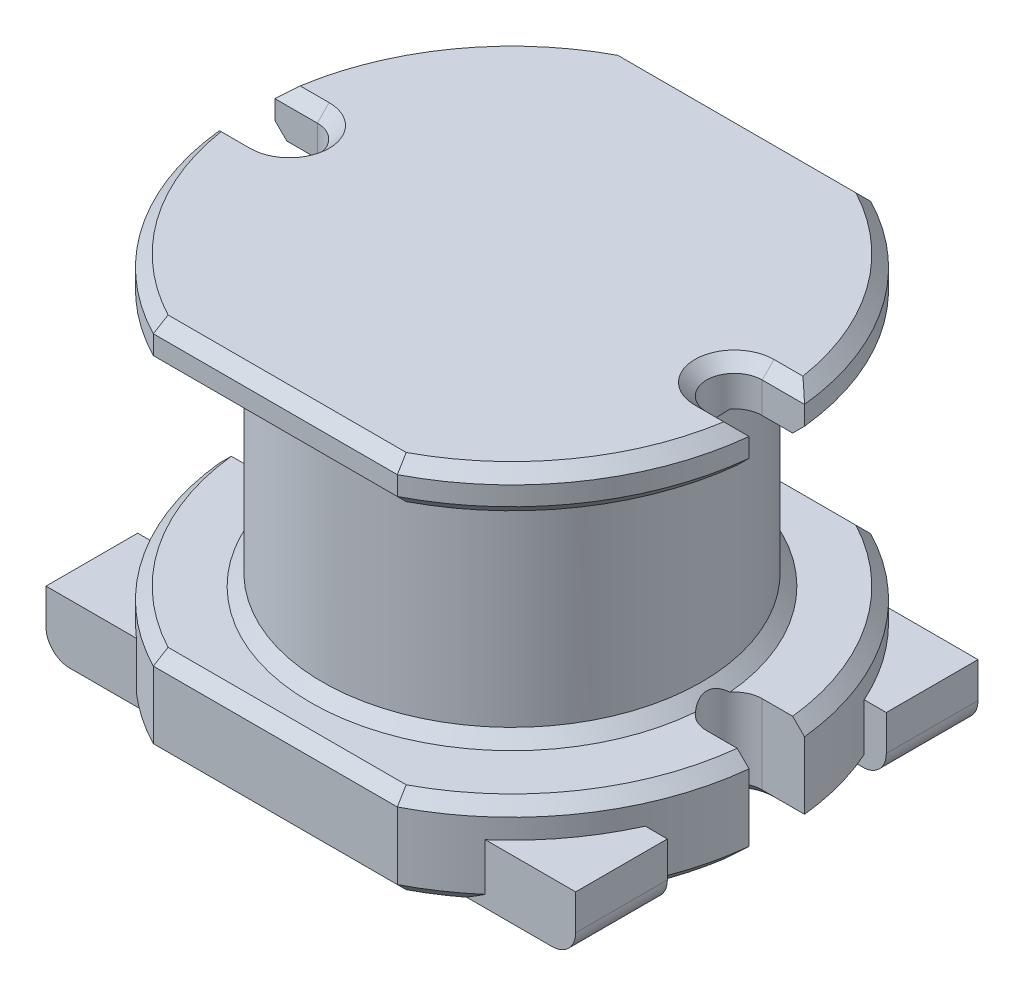
SolidWorks part; units mm, degrees
ref_plane "Спереди" through (0, 0, 0) normal (0, 0, 1) x (1, 0, 0)
ref_plane "Сверху" through (0, 0, 0) normal (0, 1, 0) x (1, 0, 0)
ref_plane "Справа" through (0, 0, 0) normal (1, 0, 0) x (0, 0, -1)
sketch "Эскиз1" plane through (0, 0, 0) normal (0, 0, 1) x (1, 0, 0)
  line L0 (0, 0) -> (2.25, 0)
  line L1 (2.25, 0) -> (2.25, 0.7678)
  line L2 (2.25, 0.7678) -> (1.6023, 0.7678)
  line L3 (1.6023, 0.7678) -> (1.6023, 2.84)
  line L4 (1.6023, 2.84) -> (2.25, 2.84)
  line L5 (2.25, 2.84) -> (2.25, 3.2)
  line L6 (2.25, 3.2) -> (0, 3.2)
  line L7 (0, 3.2) -> (0, 0)
  dimension "D1" = 2.25
  dimension "D2" = 3.2
revolve "Повернуть1" add sketch "Эскиз1" angle 360 about L7
sketch "Эскиз2" plane through (0, 3.2, 0) normal (0, 1, 0) x (1, 0, 0)
  line L1 (-2.25, -2) -> (2.25, -2)
  line L2 (-2.25, -2) -> (-2.25, 2)
  line L3 (-2.25, 2) -> (2.25, 2)
  line L4 (2.25, -2) -> (2.25, 2)
  line L5 (-2.25, -2) -> (2.25, 2) construction
  line L6 (-2.25, 2) -> (2.25, -2) construction
  line L7 (-3.4674, 2.9385) -> (3.4674, 2.9385)
  line L8 (-3.4674, 2.9385) -> (-3.4674, -2.9385)
  line L9 (-3.4674, -2.9385) -> (3.4674, -2.9385)
  line L10 (3.4674, 2.9385) -> (3.4674, -2.9385)
  line L11 (-3.4674, 2.9385) -> (3.4674, -2.9385) construction
  line L12 (-3.4674, -2.9385) -> (3.4674, 2.9385) construction
  point P0 (0, 0)
  point P6 (0, 0)
  dimension "D1" = 4
  dimension "D2" = 4.5
extrude "Вырез-Вытянуть1" cut sketch "Эскиз2" against normal through all
sketch "Эскиз3" plane through (0, 3.2, 0) normal (0, 1, 0) x (1, 0, 0)
  line L0 (0, 0) -> (0, 2.5128) construction
  line L1 (-2.6204, 0) -> (-1.8796, 0) construction
  line L2 (-2.6204, 0.2344) -> (-1.8796, 0.2344)
  line L3 (-2.6204, -0.2344) -> (-1.8796, -0.2344)
  line L4 (2.6204, 0) -> (1.8796, 0) construction
  line L5 (2.6204, 0.2344) -> (1.8796, 0.2344)
  line L6 (2.6204, -0.2344) -> (1.8796, -0.2344)
  arc A0 (-2.6204, 0.2344) -> (-2.6204, -0.2344) centre (-2.6204, 0) ccw
  arc A1 (-1.8796, -0.2344) -> (-1.8796, 0.2344) centre (-1.8796, 0) ccw
  arc A2 (-1.0308, 2) -> (-1.0308, -2) centre (0, 0) ccw construction
  arc A3 (2.6204, 0.2344) -> (2.6204, -0.2344) centre (2.6204, 0) cw
  arc A4 (1.8796, -0.2344) -> (1.8796, 0.2344) centre (1.8796, 0) cw
  point P5 (-2.25, 0)
  point P10 (-2.25, 0)
  point P14 (-1.8796, 0)
  point P17 (2.25, 0)
extrude "Вырез-Вытянуть2" cut sketch "Эскиз3" against normal through all
chamfer "Фаска1" distance 0.1 angle 45 38 edges at (-2.0587, 0, 0.2344) (-1.8575, 0, 1.2698) (0, 0, 2) (1.8575, 0, 1.2698) (2.0587, 0, 0.2344) (1.6452, 0, 0) (2.0587, 0, -0.2344) (1.8575, 0, -1.2698) (0, 0, -2) (-1.8575, 0, -1.2698) (-2.0587, 0, -0.2344) (-1.6452, 0, 0) (0, 3.2, -2) (1.8575, 3.2, -1.2698) (2.0587, 3.2, -0.2344) (1.6452, 3.2, 0) (2.0587, 3.2, 0.2344) (1.8575, 3.2, 1.2698) (0, 3.2, 2) (-1.8575, 3.2, 1.2698) (-2.0587, 3.2, 0.2344) (-1.6452, 3.2, 0) (-2.0587, 3.2, -0.2344) (-1.8575, 3.2, -1.2698) (-1.6023, 0.7678, 0) (-1.6023, 2.84, 0) (1.8575, 2.84, 1.2698) (0, 2.84, 2) (-1.8575, 2.84, 1.2698) (1.8575, 2.84, -1.2698) (0, 2.84, -2) (-1.8575, 2.84, -1.2698) (-1.8575, 0.7678, -1.2698) (0, 0.7678, -2) (1.8575, 0.7678, -1.2698) (1.8575, 0.7678, 1.2698) (0, 0.7678, 2) (-1.8575, 0.7678, 1.2698)
sketch "Эскиз4" plane through (0, 0, 0) normal (0, -1, 0) x (1, 0, 0)
  line L0 (-1.0308, 2) -> (1.0308, 2) construction
  line L1 (2.2378, -2) -> (-2.2378, -2)
  line L2 (2.2378, -2) -> (2.2378, 2)
  line L3 (2.2378, 2) -> (-2.2378, 2)
  line L4 (-2.2378, -2) -> (-2.2378, 2)
  line L5 (2.2378, -2) -> (-2.2378, 2) construction
  line L6 (2.2378, 2) -> (-2.2378, -2) construction
  line L8 (-1.05, -2) -> (1.05, -2)
  line L9 (-1.05, -2) -> (-1.05, 2)
  line L10 (-1.05, 2) -> (1.05, 2)
  line L11 (1.05, -2) -> (1.05, 2)
  line L12 (-1.05, -2) -> (1.05, 2) construction
  line L13 (-1.05, 2) -> (1.05, -2) construction
  line L14 (2.2378, -1.7) -> (-2.2378, -1.7)
  line L15 (2.2378, -1.7) -> (2.2378, 1.7)
  line L16 (2.2378, 1.7) -> (-2.2378, 1.7)
  line L17 (-2.2378, -1.7) -> (-2.2378, 1.7)
  line L18 (2.2378, -1.7) -> (-2.2378, 1.7) construction
  line L19 (2.2378, 1.7) -> (-2.2378, -1.7) construction
  line L20 (2.2378, -0.9251) -> (-2.2378, -0.9251)
  line L21 (2.2378, -0.9251) -> (2.2378, 0.9251)
  line L22 (2.2378, 0.9251) -> (-2.2378, 0.9251)
  line L23 (-2.2378, -0.9251) -> (-2.2378, 0.9251)
  line L24 (2.2378, -0.9251) -> (-2.2378, 0.9251) construction
  line L25 (2.2378, 0.9251) -> (-2.2378, -0.9251) construction
  point P0 (0, 0)
  point P9 (0, 0)
  point P14 (0, 0)
  point P19 (0, 0)
  arc M16 (-1.0062, 1.9) -> (-2.1238, 0.3344) centre (0, 0) ccw
  arc M20 (-2.1238, -0.3344) -> (-1.0062, -1.9) centre (0, 0) ccw
  arc M22 (1.0062, -1.9) -> (2.1238, -0.3344) centre (0, 0) ccw
  arc M26 (2.1238, 0.3344) -> (1.0062, 1.9) centre (0, 0) ccw
  dimension "D1" = 2.1
  dimension "D2" = 3.4
extrude "Бобышка-Вытянуть1" add sketch "Эскиз4" against normal blind 0.5 contours L22 L16 L4 M16 | L22 L2 L16 M26 | L2 L20 L14 M22 | L20 L4 L14 M20 region at (1.9298, 0, -1.3834) region at (1.9298, 0, 1.3834) region at (-1.9298, 0, -1.3834) region at (-1.9298, 0, 1.3834)
fillet "Скругление1" radius 0.2 4 edges at (2.2378, 0, 1.3125) (2.2378, 0, -1.3125) (-2.2378, 0, -1.3125) (-2.2378, 0, 1.3125)
